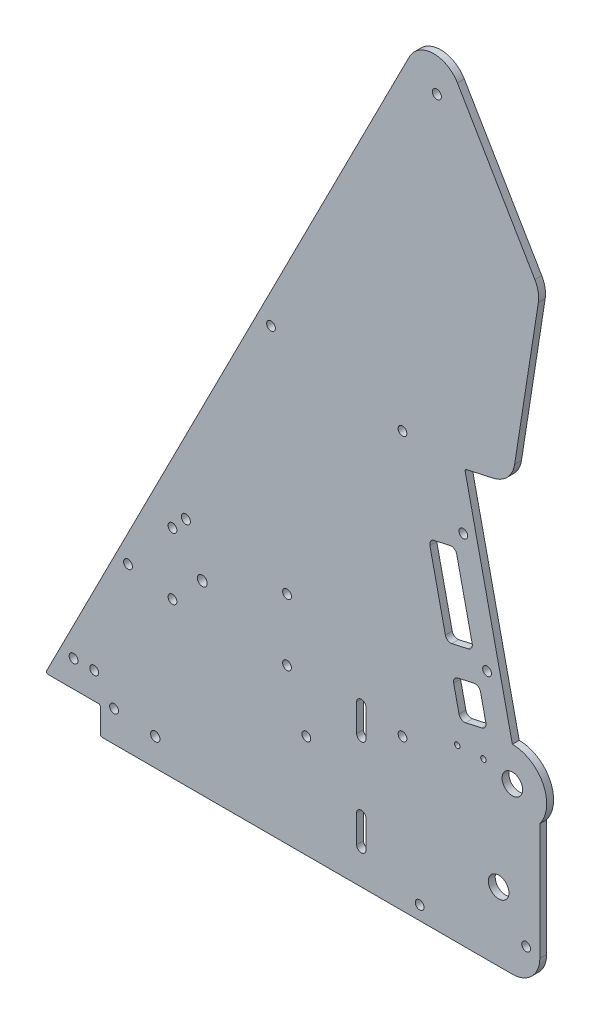
SolidWorks part; units mm, degrees
other "Markup1"
sketch "Sketch5"
ref_plane "Front Plane" through (0, 0, 0) normal (0, 0, 1) x (1, 0, 0)
ref_plane "Top Plane" through (0, 0, 0) normal (0, 1, 0) x (1, 0, 0)
ref_plane "Right Plane" through (0, 0, 0) normal (1, 0, 0) x (0, 0, -1)
sketch "Sketch1" plane through (0, 0, 0) normal (0, 0, 1) x (1, 0, 0)
  line L1 (228.6, -12.7) -> (228.6, 53.975)
  line L2 (178.7547, 351.4131) -> (0, 0)
  line L3 (228.6, 266.7) -> (178.7547, 351.4131)
  line L5 (0, 0) -> (25.4, 0)
  line L6 (25.4, 0) -> (25.4, -12.7)
  line L7 (25.4, -12.7) -> (228.6, -12.7)
  line L9 (215.9, 79.375) -> (193.9097, 178.5667)
  line L10 (193.9097, 178.5667) -> (215.6079, 183.377)
  line L11 (215.6079, 183.377) -> (228.6, 266.7)
  arc A0 (228.6, 53.975) -> (215.9, 79.375) centre (215.9, 63.5) ccw
  dimension "D7" = 12.7
  dimension "D8" = 76.2
  dimension "D10" = 31.75
  dimension "D2" = 279.4
  dimension "D3" = 25.4
  dimension "D4" = 215.9
  dimension "D5" = 394.2644
  dimension "D6" = 203.2
  dimension "D9" = 63.039
  dimension "D11" = 101.6
  dimension "D12" = 12.5
  dimension "D13" = 22.225
extrude "Boss-Extrude1" add sketch "Sketch1" along normal blind 3.175
sketch "Sketch2" plane through (0, 0, 3.175) normal (0, 0, 1) x (1, 0, 0)
  line L0 (178.7547, 351.4131) -> (0, 0) construction
  line L1 (25.4, -12.7) -> (228.6, -12.7) construction
  line L2 (215.9, 79.375) -> (193.9097, 178.5667) construction
  line L3 (193.9097, 178.5667) -> (215.6079, 183.377) construction
  line L4 (215.9, 79.375) -> (193.9097, 178.5667) construction
  line L5 (64.9432, 94.0578) -> (72.5445, 73.1732) construction
  line L6 (64.9432, 94.0578) -> (103.3734, 94.0578) construction
  line L10 (228.6, -12.7) -> (228.6, 53.975) construction
  circle A0 centre (64.9432, 94.0578) radius 2.0955
  circle A1 centre (180.975, 322.1643) radius 2.0955
  circle A2 centre (72.5445, 73.1732) radius 2.286
  circle A3 centre (193.2078, 152.3944) radius 2.032
  circle A4 centre (215.9, 63.5) radius 4.7625
  circle A7 centre (173.0375, -6.35) radius 2.032
  circle A8 centre (204.203, 102.7985) radius 2.032
  circle A26 centre (209.55, 19.05) radius 4.7625
  arc A30 (228.6, 53.975) -> (215.9, 79.375) centre (215.9, 63.5) ccw construction
  circle A31 centre (165.1, 179.3875) radius 2.032
  circle A35 centre (111.724, 87.4607) radius 2.032
  circle A36 centre (111.724, 58.8857) radius 2.032
  circle A37 centre (58.765, 58.8857) radius 2.032
  circle A38 centre (58.765, 87.4607) radius 2.032
  circle A39 centre (111.724, 58.8857) radius 1.905 construction
  circle A42 centre (111.724, 87.4607) radius 1.905 construction
  circle A43 centre (58.765, 58.8857) radius 1.905 construction
  circle A44 centre (58.765, 87.4607) radius 1.905 construction
  dimension "D3" = 4.191
  dimension "D5" = 4.191
  dimension "D9" = 4.572
  dimension "D20" = 9.525
  dimension "D23" = 9.525
  dimension "D18" = 4.064
  dimension "D26" = 4.064
  dimension "D14" = 4.064
  dimension "D10" = 4.064
  dimension "D2" = 15.24
  dimension "D6" = 15.24
  dimension "D7" = 22.225
  dimension "D21" = 44.45
  dimension "D22" = 6.35
  dimension "D19" = 160.3375
  dimension "D24" = 44.45
  dimension "D25" = 6.35
  dimension "D27" = 25.4
  dimension "D28" = 50.8
  dimension "D29" = 6.35
  dimension "D17" = 6.35
  dimension "D33" = 55.5625
  dimension "D15" = 114.3
  dimension "D4" = 180.975
  dimension "D8" = 70
extrude "Cut-Extrude1" cut sketch "Sketch2" against normal through all
sketch "Sketch7" plane through (0, 0, 3.175) normal (0, 0, 1) x (1, 0, 0)
  line L0 (146.05, 3.175) -> (146.05, 15.875) construction
  line L1 (143.891, 3.175) -> (143.891, 15.875)
  line L2 (148.209, 3.175) -> (148.209, 15.875)
  line L3 (146.05, 47.625) -> (146.05, 60.325) construction
  line L4 (143.891, 47.625) -> (143.891, 60.325)
  line L5 (148.209, 47.625) -> (148.209, 60.325)
  line L6 (25.4, -12.7) -> (228.6, -12.7) construction
  line L12 (228.6, -12.7) -> (228.6, 53.975) construction
  line L13 (25.4, -12.7) -> (228.6, -12.7) construction
  arc A0 (143.891, 3.175) -> (148.209, 3.175) centre (146.05, 3.175) ccw
  arc A1 (148.209, 15.875) -> (143.891, 15.875) centre (146.05, 15.875) ccw
  arc A2 (143.891, 47.625) -> (148.209, 47.625) centre (146.05, 47.625) ccw
  arc A3 (148.209, 60.325) -> (143.891, 60.325) centre (146.05, 60.325) ccw
  circle A8 centre (50.8, 0) radius 2.159
  point P2 (146.05, 9.525)
  point P9 (146.05, 53.975)
  dimension "D1" = 4.318
  dimension "D5" = 4.318
  dimension "D2" = 12.7
  dimension "D3" = 12.7
  dimension "D4" = 44.45
  dimension "D6" = 95.25
  dimension "D7" = 82.55
  dimension "D8" = 15.875
  dimension "D9" = 12.7
extrude "Cut-Extrude2" cut sketch "Sketch7" against normal through all
sketch "Sketch10" plane through (0, 0, 3.175) normal (0, 0, 1) x (1, 0, 0)
  circle A0 centre (120.65, 34.925) radius 2.032
  circle A1 centre (165.1, 57.15) radius 2.032
  circle A2 centre (13.0465, 12.3347) radius 2.032
  circle A3 centre (22.5715, 12.3347) radius 2.032
  circle A4 centre (38.2114, 62.6398) radius 2.032
  dimension "D1" = 4.064
  dimension "D3" = 34.925
  dimension "D2" = 120.65
  dimension "D4" = 63.5
  dimension "D5" = 69.85
extrude "Cut-Extrude3" cut sketch "Sketch10" against normal up to next
fillet "Fillet1" radius 12.7 4 edges at (228.6, -12.7, 1.5875) (178.7547, 351.4131, 1.5875) (215.6079, 183.377, 1.5875) (228.6, 266.7, 1.5875)
fillet "Fillet2" radius 0.7937 4 edges at (25.4, -12.7, 1.5875) (25.4, 0, 1.5875) (193.9097, 178.5667, 1.5875) (0, 0, 1.5875)
sketch "Sketch12" plane through (0, 0, 3.175) normal (0, 0, 1) x (1, 0, 0)
  circle A0 centre (31.75, 1.5875) radius 2.032
  circle A1 centre (173.0375, -6.35) radius 2.032
  circle A2 centre (222.25, 1.5875) radius 2.032
  dimension "D1" = 4.064
extrude "Cut-Extrude5" cut sketch "Sketch12" against normal through all
sketch "Sketch13" plane through (0, 0, 3.175) normal (0, 0, 1) x (1, 0, 0)
  line L0 (168.2448, 330.7518) -> (0.5868, 1.1536) construction
  circle A0 centre (104.3218, 191.08) radius 2.032
  dimension "D2" = 4.064
  dimension "D1" = 6.35
extrude "Cut-Extrude6" cut sketch "Sketch13" against normal through all
sketch "Sketch14" plane through (0, 0, 3.175) normal (0, 0, 1) x (1, 0, 0)
  line L0 (177.2237, 142.3466) -> (189.6226, 145.0954)
  line L1 (189.6226, 145.0954) -> (197.869, 107.8985)
  line L2 (197.869, 107.8985) -> (185.47, 105.1497)
  line L3 (185.47, 105.1497) -> (177.2237, 142.3466)
  line L4 (187.1428, 144.5456) -> (179.7035, 142.8963) construction
  line L5 (188.2188, 92.7508) -> (200.6178, 95.4995)
  line L6 (188.2188, 92.7508) -> (191.7922, 76.6321)
  line L7 (191.7922, 76.6321) -> (204.1912, 79.3809)
  line L8 (200.6178, 95.4995) -> (204.1912, 79.3809)
  line L11 (197.3192, 110.3783) -> (190.1724, 142.6156) construction
  line L12 (177.7734, 139.8668) -> (184.9203, 107.6295) construction
  line L13 (187.9498, 105.6995) -> (195.3892, 107.3487) construction
  line L14 (203.6414, 81.8607) -> (201.1675, 93.0197) construction
  line L15 (194.272, 77.1819) -> (201.7114, 78.8311) construction
  line L16 (188.7686, 90.271) -> (191.2425, 79.1119) construction
  line L17 (198.138, 94.9498) -> (190.6986, 93.3005) construction
  circle A0 centre (190.4268, 66.2609) radius 1.27
  circle A1 centre (202.5335, 66.7895) radius 1.27
  circle A2 centre (190.4268, 66.2609) radius 1.27 construction
  circle A3 centre (202.5335, 66.7895) radius 1.27 construction
  point P8 (152.4, 88.9)
extrude "Cut-Extrude7" cut sketch "Sketch14" against normal through all both and the other way through all
fillet "Fillet3" radius 2.54 8 edges at (200.6178, 95.4995, 1.5875) (188.2188, 92.7508, 1.5875) (191.7922, 76.6321, 1.5875) (204.1912, 79.3809, 1.5875) (197.869, 107.8985, 1.5875) (185.47, 105.1497, 1.5875) (177.2237, 142.3466, 1.5875) (189.6226, 145.0954, 1.5875)
equation "\"D6@Sketch2\"=\"D2@Sketch2\""
